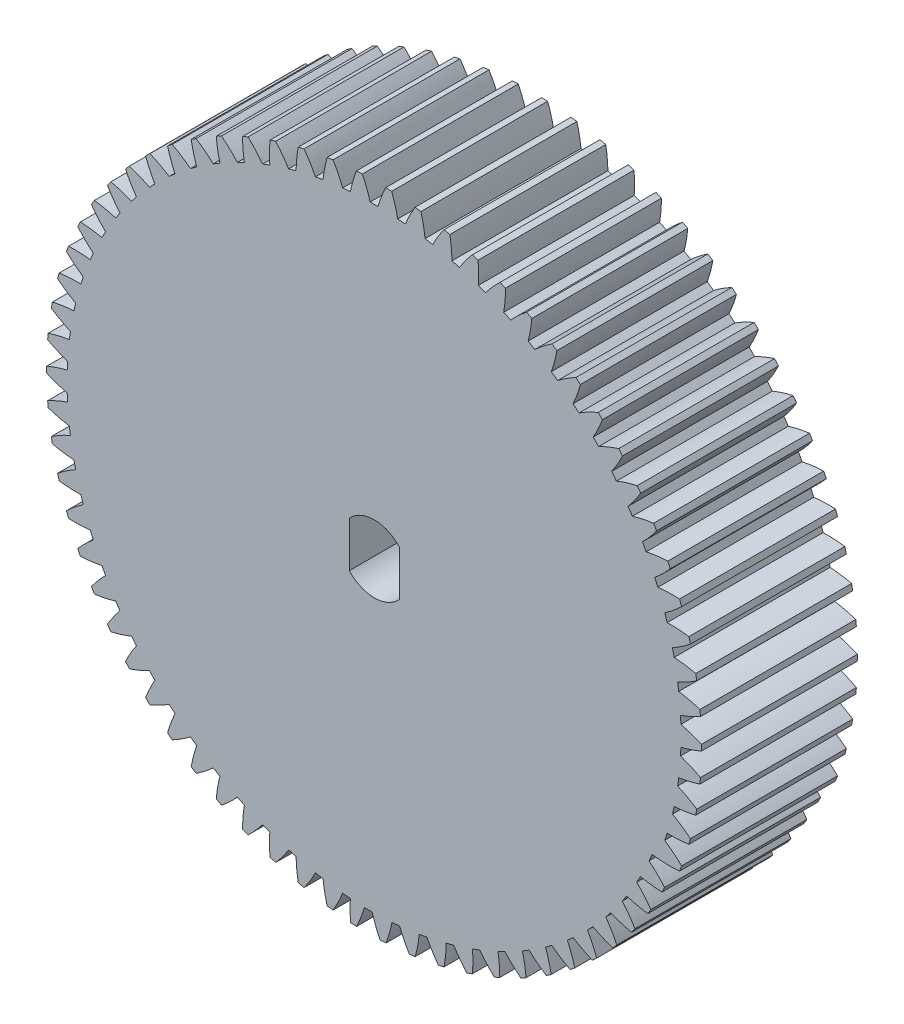
SolidWorks part; units mm, degrees
material "ABS"
ref_plane "Alzado" through (0, 0, 0) normal (0, 0, 1) x (1, 0, 0)
ref_plane "Planta" through (0, 0, 0) normal (0, 1, 0) x (1, 0, 0)
ref_plane "Vista lateral" through (0, 0, 0) normal (1, 0, 0) x (0, 0, -1)
sketch "Croquis1" plane through (0, 0, 0) normal (0, 0, 1) x (1, 0, 0)
  line L0 (-0.0534, 0.0662) -> (-0.0534, 2.6662) construction
  line L1 (-0.0534, 0.0662) -> (-0.0534, 2.6662) construction
  line L4 (-1.9784, 1.8138) -> (-1.9784, -1.6815)
  line L5 (1.8716, 1.8138) -> (1.8716, -1.6815)
  arc A0 (-25.274, -0.1619) -> (-23.6867, -0.6961) centre (-21.3661, 8.8252) ccw
  arc A1 (-23.6867, -0.6961) -> (-23.66, -1.2912) centre (-0.0534, 0.0662) ccw
  arc A2 (-23.66, -1.2912) -> (-25.193, -1.9655) centre (-20.4953, -10.5662) ccw
  arc A3 (-25.193, -1.9655) -> (-25.1521, -2.4198) centre (-0.075, 0.0662) ccw
  arc A4 (-25.1521, -2.4198) -> (-23.5233, -2.8095) centre (-22.0656, 6.8814) ccw
  arc A5 (-23.5233, -2.8095) -> (-23.4434, -3.3999) centre (-0.075, 0.0662) ccw
  arc A6 (-23.4434, -3.3999) -> (-24.9097, -4.2089) centre (-19.46, -12.3538) ccw
  arc A7 (-24.9097, -4.2089) -> (-24.8283, -4.6577) centre (-0.075, 0.0662) ccw
  arc A8 (-24.8283, -4.6577) -> (-23.1711, -4.8999) centre (-22.588, 4.8828) ccw
  arc A9 (-23.1711, -4.8999) -> (-23.0386, -5.4807) centre (-0.075, 0.0662) ccw
  arc A10 (-23.0386, -5.4807) -> (-24.4265, -6.4178) centre (-18.2686, -14.0415) ccw
  arc A11 (-24.4265, -6.4178) -> (-24.3052, -6.8576) centre (-0.075, 0.0662) ccw
  arc A12 (-24.3052, -6.8576) -> (-22.633, -6.9502) centre (-22.9291, 2.8453) ccw
  arc A13 (-22.633, -6.9502) -> (-22.4489, -7.5168) centre (-0.075, 0.0662) ccw
  arc A14 (-22.4489, -7.5168) -> (-23.7473, -8.5746) centre (-16.9308, -15.6156) ccw
  arc A15 (-23.7473, -8.5746) -> (-23.587, -9.0017) centre (-0.075, 0.0662) ccw
  arc A16 (-23.587, -9.0017) -> (-21.9133, -8.944) centre (-23.0862, 0.7855) ccw
  arc A17 (-21.9133, -8.944) -> (-21.6791, -9.4918) centre (-0.075, 0.0662) ccw
  arc A18 (-21.6791, -9.4918) -> (-22.8774, -10.6618) centre (-15.4572, -17.0634) ccw
  arc A19 (-22.8774, -10.6618) -> (-22.6795, -11.0728) centre (-0.075, 0.0662) ccw
  arc A20 (-22.6795, -11.0728) -> (-21.0177, -10.8653) centre (-23.0581, -1.2801) ccw
  arc A21 (-21.0177, -10.8653) -> (-20.7354, -11.3899) centre (-0.075, 0.0662) ccw
  arc A22 (-20.7354, -11.3899) -> (-21.824, -12.6626) centre (-13.8598, -18.3733) ccw
  arc A23 (-21.824, -12.6626) -> (-21.59, -13.0542) centre (-0.075, 0.0662) ccw
  arc A24 (-21.59, -13.0542) -> (-19.9535, -12.6986) centre (-22.8449, -3.3348) ccw
  arc A25 (-19.9535, -12.6986) -> (-19.6253, -13.1958) centre (-0.075, 0.0662) ccw
  arc A26 (-19.6253, -13.1958) -> (-20.5955, -14.5609) centre (-12.1514, -19.5347) ccw
  arc A27 (-20.5955, -14.5609) -> (-20.3273, -14.9299) centre (-0.075, 0.0662) ccw
  arc A28 (-20.3273, -14.9299) -> (-18.7292, -14.4291) centre (-22.4483, -5.3622) ccw
  arc A29 (-18.7292, -14.4291) -> (-18.3578, -14.8949) centre (-0.075, 0.0662) ccw
  arc A30 (-18.3578, -14.8949) -> (-19.2017, -16.3415) centre (-10.3458, -20.5383) ccw
  arc A31 (-19.2017, -16.3415) -> (-18.9016, -16.685) centre (-0.075, 0.0662) ccw
  arc A32 (-18.9016, -16.685) -> (-17.3548, -16.0429) centre (-21.8717, -7.3459) ccw
  arc A33 (-17.3548, -16.0429) -> (-16.9431, -16.4735) centre (-0.075, 0.0662) ccw
  arc A34 (-16.9431, -16.4735) -> (-17.6539, -17.9899) centre (-8.4575, -21.376) ccw
  arc A35 (-17.6539, -17.9899) -> (-17.3242, -18.3051) centre (-0.075, 0.0662) ccw
  arc A36 (-17.3242, -18.3051) -> (-15.8412, -17.527) centre (-21.1195, -9.2699) ccw
  arc A37 (-15.8412, -17.527) -> (-15.3926, -17.919) centre (-0.075, 0.0662) ccw
  arc A38 (-15.3926, -17.919) -> (-15.9646, -19.493) centre (-6.5017, -22.0411) ccw
  arc A39 (-15.9646, -19.493) -> (-15.608, -19.7774) centre (-0.075, 0.0662) ccw
  arc A40 (-15.608, -19.7774) -> (-14.2007, -18.8695) centre (-20.1979, -11.1187) ccw
  arc A41 (-14.2007, -18.8695) -> (-13.7187, -19.2196) centre (-0.075, 0.0662) ccw
  arc A42 (-13.7187, -19.2196) -> (-14.1474, -20.8386) centre (-4.4941, -22.5282) ccw
  arc A43 (-14.1474, -20.8386) -> (-13.7667, -21.0899) centre (-0.075, 0.0662) ccw
  arc A44 (-13.7667, -21.0899) -> (-12.4465, -20.0594) centre (-19.1143, -12.8775) ccw
  arc A45 (-12.4465, -20.0594) -> (-11.9351, -20.365) centre (-0.075, 0.0662) ccw
  arc A46 (-11.9351, -20.365) -> (-12.2169, -22.0159) centre (-2.451, -22.8334) ccw
  arc A47 (-12.2169, -22.0159) -> (-11.8151, -22.232) centre (-0.075, 0.0662) ccw
  arc A48 (-11.8151, -22.232) -> (-10.5926, -21.0874) centre (-17.8774, -14.5321) ccw
  arc A49 (-10.5926, -21.0874) -> (-10.0559, -21.3459) centre (-0.075, 0.0662) ccw
  arc A50 (-10.0559, -21.3459) -> (-10.1886, -23.0153) centre (-0.3887, -22.9542) ccw
  arc A51 (-10.1886, -23.0153) -> (-9.7691, -23.1946) centre (-0.075, 0.0662) ccw
  arc A52 (-9.7691, -23.1946) -> (-8.6541, -21.945) centre (-16.4972, -16.0691) ccw
  arc A53 (-8.6541, -21.945) -> (-8.0963, -22.1544) centre (-0.075, 0.0662) ccw
  arc A54 (-8.0963, -22.1544) -> (-8.0788, -23.829) centre (1.676, -22.8896) ccw
  arc A55 (-8.0788, -23.829) -> (-7.645, -23.97) centre (-0.075, 0.0662) ccw
  arc A56 (-7.645, -23.97) -> (-6.6465, -22.6254) centre (-14.9847, -17.4762) ccw
  arc A57 (-6.6465, -22.6254) -> (-6.0722, -22.7839) centre (-0.075, 0.0662) ccw
  arc A58 (-6.0722, -22.7839) -> (-5.9047, -24.4503) centre (3.7267, -22.6402) ccw
  arc A59 (-5.9047, -24.4503) -> (-5.4599, -24.5518) centre (-0.075, 0.0662) ccw
  arc A60 (-5.4599, -24.5518) -> (-4.586, -23.1232) centre (-13.3522, -18.7421) ccw
  arc A61 (-4.586, -23.1232) -> (-3.9998, -23.2295) centre (-0.075, 0.0662) ccw
  arc A62 (-3.9998, -23.2295) -> (-3.6836, -24.8741) centre (5.7468, -22.2081) ccw
  arc A63 (-3.6836, -24.8741) -> (-3.2315, -24.9354) centre (-0.075, 0.0662) ccw
  arc A64 (-3.2315, -24.9354) -> (-2.4891, -23.4342) centre (-11.6128, -19.8565) ccw
  arc A65 (-2.4891, -23.4342) -> (-1.8958, -23.4876) centre (-0.075, 0.0662) ccw
  arc A66 (-1.8958, -23.4876) -> (-1.875, -25.0972) centre (7.8807, -24.1662) ccw
  arc A67 (-1.875, -25.0972) -> (-1.4193, -25.1177) centre (-0.5166, 0.0662) ccw
  arc A68 (-1.4193, -25.1177) -> (-0.8145, -23.556) centre (-10.2221, -20.8106) ccw
  arc A69 (-0.8145, -23.556) -> (-0.2187, -23.556) centre (-0.5166, 0.0662) ccw
  arc A70 (-0.2187, -23.556) -> (0.3861, -25.1177) centre (9.1889, -20.8106) ccw
  arc A71 (0.3861, -25.1177) -> (0.8418, -25.0972) centre (-0.5166, 0.0662) ccw
  arc A72 (0.8418, -25.0972) -> (1.3042, -23.4876) centre (-8.3116, -21.5965) ccw
  arc A73 (1.3042, -23.4876) -> (1.8976, -23.4342) centre (-0.5166, 0.0662) ccw
  arc A74 (1.8976, -23.4342) -> (2.6399, -24.9354) centre (11.0212, -19.8565) ccw
  arc A75 (2.6399, -24.9354) -> (3.092, -24.8741) centre (-0.5166, 0.0662) ccw
  arc A76 (3.092, -24.8741) -> (3.4082, -23.2295) centre (-6.3384, -22.2081) ccw
  arc A77 (3.4082, -23.2295) -> (3.9944, -23.1232) centre (-0.5166, 0.0662) ccw
  arc A78 (3.9944, -23.1232) -> (4.8683, -24.5518) centre (12.7606, -18.7421) ccw
  arc A79 (4.8683, -24.5518) -> (5.3131, -24.4503) centre (-0.5166, 0.0662) ccw
  arc A80 (5.3131, -24.4503) -> (5.4806, -22.7839) centre (-4.3183, -22.6402) ccw
  arc A81 (5.4806, -22.7839) -> (6.0549, -22.6254) centre (-0.5166, 0.0662) ccw
  arc A82 (6.0549, -22.6254) -> (7.0534, -23.97) centre (14.3931, -17.4762) ccw
  arc A83 (7.0534, -23.97) -> (7.4872, -23.829) centre (-0.5166, 0.0662) ccw
  arc A84 (7.4872, -23.829) -> (7.5047, -22.1544) centre (-2.2676, -22.8896) ccw
  arc A85 (7.5047, -22.1544) -> (8.0625, -21.945) centre (-0.5166, 0.0662) ccw
  arc A86 (8.0625, -21.945) -> (9.1775, -23.1946) centre (15.9056, -16.0691) ccw
  arc A87 (9.1775, -23.1946) -> (9.597, -23.0153) centre (-0.5166, 0.0662) ccw
  arc A88 (9.597, -23.0153) -> (9.4643, -21.3459) centre (-0.2028, -22.9542) ccw
  arc A89 (9.4643, -21.3459) -> (10.001, -21.0874) centre (-0.5166, 0.0662) ccw
  arc A90 (10.001, -21.0874) -> (11.2236, -22.232) centre (17.2858, -14.5321) ccw
  arc A91 (11.2236, -22.232) -> (11.6253, -22.0159) centre (-0.5166, 0.0662) ccw
  arc A92 (11.6253, -22.0159) -> (11.3435, -20.365) centre (1.8594, -22.8334) ccw
  arc A93 (11.3435, -20.365) -> (11.8549, -20.0594) centre (-0.5166, 0.0662) ccw
  arc A94 (11.8549, -20.0594) -> (13.1751, -21.0899) centre (18.5227, -12.8775) ccw
  arc A95 (13.1751, -21.0899) -> (13.5558, -20.8386) centre (-0.5166, 0.0662) ccw
  arc A96 (13.5558, -20.8386) -> (13.1272, -19.2196) centre (3.9025, -22.5282) ccw
  arc A97 (13.1272, -19.2196) -> (13.6091, -18.8695) centre (-0.5166, 0.0662) ccw
  arc A98 (13.6091, -18.8695) -> (15.0164, -19.7774) centre (19.6063, -11.1187) ccw
  arc A99 (15.0164, -19.7774) -> (15.373, -19.493) centre (-0.5166, 0.0662) ccw
  arc A100 (15.373, -19.493) -> (14.801, -17.919) centre (5.9101, -22.0411) ccw
  arc A101 (14.801, -17.919) -> (15.2496, -17.527) centre (-0.5166, 0.0662) ccw
  arc A102 (15.2496, -17.527) -> (16.7326, -18.3051) centre (20.5279, -9.2699) ccw
  arc A103 (16.7326, -18.3051) -> (17.0623, -17.9899) centre (-0.5166, 0.0662) ccw
  arc A104 (17.0623, -17.9899) -> (16.3515, -16.4735) centre (7.8659, -21.376) ccw
  arc A105 (16.3515, -16.4735) -> (16.7632, -16.0429) centre (-0.5166, 0.0662) ccw
  arc A106 (16.7632, -16.0429) -> (18.31, -16.685) centre (21.2801, -7.3459) ccw
  arc A107 (18.31, -16.685) -> (18.6101, -16.3415) centre (-0.5166, 0.0662) ccw
  arc A108 (18.6101, -16.3415) -> (17.7662, -14.8949) centre (9.7542, -20.5383) ccw
  arc A109 (17.7662, -14.8949) -> (18.1376, -14.4291) centre (-0.5166, 0.0662) ccw
  arc A110 (18.1376, -14.4291) -> (19.7357, -14.9299) centre (21.8568, -5.3622) ccw
  arc A111 (19.7357, -14.9299) -> (20.0039, -14.5609) centre (-0.5166, 0.0662) ccw
  arc A112 (20.0039, -14.5609) -> (19.0337, -13.1958) centre (11.5599, -19.5347) ccw
  arc A113 (19.0337, -13.1958) -> (19.3619, -12.6986) centre (-0.5166, 0.0662) ccw
  arc A114 (19.3619, -12.6986) -> (20.9984, -13.0542) centre (22.2533, -3.3348) ccw
  arc A115 (20.9984, -13.0542) -> (21.2324, -12.6626) centre (-0.5166, 0.0662) ccw
  arc A116 (21.2324, -12.6626) -> (20.1438, -11.3899) centre (13.2682, -18.3733) ccw
  arc A117 (20.1438, -11.3899) -> (20.4261, -10.8653) centre (-0.5166, 0.0662) ccw
  arc A118 (20.4261, -10.8653) -> (22.0879, -11.0728) centre (22.4665, -1.2801) ccw
  arc A119 (22.0879, -11.0728) -> (22.2859, -10.6618) centre (-0.5166, 0.0662) ccw
  arc A120 (22.2859, -10.6618) -> (21.0875, -9.4918) centre (14.8656, -17.0634) ccw
  arc A121 (21.0875, -9.4918) -> (21.3217, -8.944) centre (-0.5166, 0.0662) ccw
  arc A122 (21.3217, -8.944) -> (23.437, -9.0017) centre (22.6447, 0.7663) ccw
  arc A123 (23.437, -9.0017) -> (23.5973, -8.5746) centre (-0.075, 0.0662) ccw
  arc A124 (23.5973, -8.5746) -> (22.2989, -7.5168) centre (16.7808, -15.6156) ccw
  arc A125 (22.2989, -7.5168) -> (22.483, -6.9502) centre (-0.075, 0.0662) ccw
  arc A126 (22.483, -6.9502) -> (24.1552, -6.8576) centre (22.7791, 2.8453) ccw
  arc A127 (24.1552, -6.8576) -> (24.2765, -6.4178) centre (-0.075, 0.0662) ccw
  arc A128 (24.2765, -6.4178) -> (22.8886, -5.4807) centre (18.1186, -14.0415) ccw
  arc A129 (22.8886, -5.4807) -> (23.0211, -4.8999) centre (-0.075, 0.0662) ccw
  arc A130 (23.0211, -4.8999) -> (24.6783, -4.6577) centre (22.438, 4.8828) ccw
  arc A131 (24.6783, -4.6577) -> (24.7597, -4.2089) centre (-0.075, 0.0662) ccw
  arc A132 (24.7597, -4.2089) -> (23.2934, -3.3999) centre (19.31, -12.3538) ccw
  arc A133 (23.2934, -3.3999) -> (23.3733, -2.8095) centre (-0.075, 0.0662) ccw
  arc A134 (23.3733, -2.8095) -> (25.0021, -2.4198) centre (21.9156, 6.8814) ccw
  arc A135 (25.0021, -2.4198) -> (25.043, -1.9655) centre (-0.075, 0.0662) ccw
  arc A136 (25.043, -1.9655) -> (23.51, -1.2912) centre (20.3453, -10.5662) ccw
  arc A137 (23.51, -1.2912) -> (23.5367, -0.6961) centre (-0.075, 0.0662) ccw
  arc A138 (23.5367, -0.6961) -> (25.124, -0.1619) centre (21.2161, 8.8252) ccw
  arc A139 (25.124, -0.1619) -> (25.124, 0.2942) centre (-0.075, 0.0662) ccw
  arc A140 (25.124, 0.2942) -> (23.5367, 0.8284) centre (21.2161, -8.6929) ccw
  arc A141 (23.5367, 0.8284) -> (23.51, 1.4235) centre (-0.075, 0.0662) ccw
  arc A142 (23.51, 1.4235) -> (25.043, 2.0978) centre (20.3453, 10.6985) ccw
  arc A143 (25.043, 2.0978) -> (25.0021, 2.5521) centre (-0.075, 0.0662) ccw
  arc A144 (25.0021, 2.5521) -> (23.3733, 2.9419) centre (21.9156, -6.7491) ccw
  arc A145 (23.3733, 2.9419) -> (23.2934, 3.5322) centre (-0.075, 0.0662) ccw
  arc A146 (23.2934, 3.5322) -> (24.7597, 4.3412) centre (19.31, 12.4861) ccw
  arc A147 (24.7597, 4.3412) -> (24.6783, 4.79) centre (-0.075, 0.0662) ccw
  arc A148 (24.6783, 4.79) -> (23.0211, 5.0322) centre (22.438, -4.7505) ccw
  arc A149 (23.0211, 5.0322) -> (22.8886, 5.613) centre (-0.075, 0.0662) ccw
  arc A150 (22.8886, 5.613) -> (24.2765, 6.5501) centre (18.1186, 14.1738) ccw
  arc A151 (24.2765, 6.5501) -> (24.1552, 6.9899) centre (-0.075, 0.0662) ccw
  arc A152 (24.1552, 6.9899) -> (22.483, 7.0825) centre (22.7791, -2.713) ccw
  arc A153 (22.483, 7.0825) -> (22.2989, 7.6491) centre (-0.075, 0.0662) ccw
  arc A154 (22.2989, 7.6491) -> (23.5973, 8.7069) centre (16.7808, 15.7479) ccw
  arc A155 (23.5973, 8.7069) -> (23.437, 9.134) centre (-0.075, 0.0662) ccw
  arc A156 (23.437, 9.134) -> (21.7633, 9.0763) centre (22.9362, -0.6532) ccw
  arc A157 (21.7633, 9.0763) -> (21.5291, 9.6241) centre (-0.075, 0.0662) ccw
  arc A158 (21.5291, 9.6241) -> (22.7274, 10.7941) centre (15.3072, 17.1957) ccw
  arc A159 (22.7274, 10.7941) -> (22.5295, 11.2051) centre (-0.075, 0.0662) ccw
  arc A160 (22.5295, 11.2051) -> (20.8677, 10.9976) centre (22.9081, 1.4124) ccw
  arc A161 (20.8677, 10.9976) -> (20.5854, 11.5223) centre (-0.075, 0.0662) ccw
  arc A162 (20.5854, 11.5223) -> (21.674, 12.7949) centre (13.7098, 18.5056) ccw
  arc A163 (21.674, 12.7949) -> (21.44, 13.1865) centre (-0.075, 0.0662) ccw
  arc A164 (21.44, 13.1865) -> (19.8035, 12.8309) centre (22.6949, 3.4672) ccw
  arc A165 (19.8035, 12.8309) -> (19.4753, 13.3281) centre (-0.075, 0.0662) ccw
  arc A166 (19.4753, 13.3281) -> (20.4455, 14.6932) centre (12.0014, 19.667) ccw
  arc A167 (20.4455, 14.6932) -> (20.1773, 15.0623) centre (-0.075, 0.0662) ccw
  arc A168 (20.1773, 15.0623) -> (18.5792, 14.5614) centre (22.2983, 5.4945) ccw
  arc A169 (18.5792, 14.5614) -> (18.2078, 15.0272) centre (-0.075, 0.0662) ccw
  arc A170 (18.2078, 15.0272) -> (19.0517, 16.4738) centre (10.1958, 20.6706) ccw
  arc A171 (19.0517, 16.4738) -> (18.7516, 16.8173) centre (-0.075, 0.0662) ccw
  arc A172 (18.7516, 16.8173) -> (17.2048, 16.1752) centre (21.7217, 7.4782) ccw
  arc A173 (17.2048, 16.1752) -> (16.7931, 16.6058) centre (-0.075, 0.0662) ccw
  arc A174 (16.7931, 16.6058) -> (17.5039, 18.1222) centre (8.3075, 21.5084) ccw
  arc A175 (17.5039, 18.1222) -> (17.1742, 18.4375) centre (-0.075, 0.0662) ccw
  arc A176 (17.1742, 18.4375) -> (15.6912, 17.6593) centre (20.9695, 9.4022) ccw
  arc A177 (15.6912, 17.6593) -> (15.2426, 18.0513) centre (-0.075, 0.0662) ccw
  arc A178 (15.2426, 18.0513) -> (15.8146, 19.6253) centre (6.3517, 22.1734) ccw
  arc A179 (15.8146, 19.6253) -> (15.458, 19.9097) centre (-0.075, 0.0662) ccw
  arc A180 (15.458, 19.9097) -> (14.0507, 19.0018) centre (20.0479, 11.2511) ccw
  arc A181 (14.0507, 19.0018) -> (13.5687, 19.3519) centre (-0.075, 0.0662) ccw
  arc A182 (13.5687, 19.3519) -> (13.9974, 20.9709) centre (4.3441, 22.6605) ccw
  arc A183 (13.9974, 20.9709) -> (13.6167, 21.2222) centre (-0.075, 0.0662) ccw
  arc A184 (13.6167, 21.2222) -> (12.2965, 20.1918) centre (18.9643, 13.0098) ccw
  arc A185 (12.2965, 20.1918) -> (11.7851, 20.4973) centre (-0.075, 0.0662) ccw
  arc A186 (11.7851, 20.4973) -> (12.0669, 22.1482) centre (2.301, 22.9657) ccw
  arc A187 (12.0669, 22.1482) -> (11.6651, 22.3643) centre (-0.075, 0.0662) ccw
  arc A188 (11.6651, 22.3643) -> (10.4426, 21.2197) centre (17.7274, 14.6644) ccw
  arc A189 (10.4426, 21.2197) -> (9.9059, 21.4782) centre (-0.075, 0.0662) ccw
  arc A190 (9.9059, 21.4782) -> (10.0386, 23.1477) centre (0.2387, 23.0865) ccw
  arc A191 (10.0386, 23.1477) -> (9.6191, 23.327) centre (-0.075, 0.0662) ccw
  arc A192 (9.6191, 23.327) -> (8.5041, 22.0773) centre (16.3472, 16.2014) ccw
  arc A193 (8.5041, 22.0773) -> (7.9463, 22.2867) centre (-0.075, 0.0662) ccw
  arc A194 (7.9463, 22.2867) -> (7.9288, 23.9613) centre (-1.826, 23.0219) ccw
  arc A195 (7.9288, 23.9613) -> (7.495, 24.1023) centre (-0.075, 0.0662) ccw
  arc A196 (7.495, 24.1023) -> (6.4965, 22.7578) centre (14.8347, 17.6085) ccw
  arc A197 (6.4965, 22.7578) -> (5.9222, 22.9163) centre (-0.075, 0.0662) ccw
  arc A198 (5.9222, 22.9163) -> (5.7547, 24.5826) centre (-3.8767, 22.7726) ccw
  arc A199 (5.7547, 24.5826) -> (5.3099, 24.6841) centre (-0.075, 0.0662) ccw
  arc A200 (5.3099, 24.6841) -> (4.436, 23.2555) centre (13.2022, 18.8744) ccw
  arc A201 (4.436, 23.2555) -> (3.8498, 23.3619) centre (-0.075, 0.0662) ccw
  arc A202 (3.8498, 23.3619) -> (3.5336, 25.0065) centre (-5.8968, 22.3404) ccw
  arc A203 (3.5336, 25.0065) -> (3.0815, 25.0677) centre (-0.075, 0.0662) ccw
  arc A204 (3.0815, 25.0677) -> (2.3391, 23.5665) centre (11.4628, 19.9889) ccw
  arc A205 (2.3391, 23.5665) -> (1.7458, 23.6199) centre (-0.075, 0.0662) ccw
  arc A206 (1.7458, 23.6199) -> (1.2834, 25.2295) centre (-7.87, 21.7288) ccw
  arc A207 (1.2834, 25.2295) -> (0.8277, 25.25) centre (-0.075, 0.0662) ccw
  arc A208 (0.8277, 25.25) -> (0.2229, 23.6883) centre (9.6305, 20.9429) ccw
  arc A209 (0.2229, 23.6883) -> (-0.3729, 23.6883) centre (-0.075, 0.0662) ccw
  arc A210 (-0.3729, 23.6883) -> (-0.9777, 25.25) centre (-9.7805, 20.9429) ccw
  arc A211 (-0.9777, 25.25) -> (-1.4334, 25.2295) centre (-0.075, 0.0662) ccw
  arc A212 (-1.4334, 25.2295) -> (-1.8958, 23.6199) centre (7.72, 21.7288) ccw
  arc A213 (-1.8958, 23.6199) -> (-2.4891, 23.5665) centre (-0.075, 0.0662) ccw
  arc A214 (-2.4891, 23.5665) -> (-3.2315, 25.0677) centre (-11.6128, 19.9889) ccw
  arc A215 (-3.2315, 25.0677) -> (-3.6836, 25.0065) centre (-0.075, 0.0662) ccw
  arc A216 (-3.6836, 25.0065) -> (-3.9998, 23.3619) centre (5.7468, 22.3404) ccw
  arc A217 (-3.9998, 23.3619) -> (-4.586, 23.2555) centre (-0.075, 0.0662) ccw
  arc A218 (-4.586, 23.2555) -> (-5.4599, 24.6841) centre (-13.3522, 18.8744) ccw
  arc A219 (-5.4599, 24.6841) -> (-5.9047, 24.5826) centre (-0.075, 0.0662) ccw
  arc A220 (-5.9047, 24.5826) -> (-6.0722, 22.9163) centre (3.7267, 22.7726) ccw
  arc A221 (-6.0722, 22.9163) -> (-6.6465, 22.7578) centre (-0.075, 0.0662) ccw
  arc A222 (-6.6465, 22.7578) -> (-7.645, 24.1023) centre (-14.9847, 17.6085) ccw
  arc A223 (-7.645, 24.1023) -> (-8.0788, 23.9613) centre (-0.075, 0.0662) ccw
  arc A224 (-8.0788, 23.9613) -> (-8.0963, 22.2867) centre (1.676, 23.0219) ccw
  arc A225 (-8.0963, 22.2867) -> (-8.6541, 22.0773) centre (-0.075, 0.0662) ccw
  arc A226 (-8.6541, 22.0773) -> (-9.7691, 23.327) centre (-16.4972, 16.2014) ccw
  arc A227 (-9.7691, 23.327) -> (-10.1886, 23.1477) centre (-0.075, 0.0662) ccw
  arc A228 (-10.1886, 23.1477) -> (-10.0559, 21.4782) centre (-0.3887, 23.0865) ccw
  arc A229 (-10.0559, 21.4782) -> (-10.5926, 21.2197) centre (-0.075, 0.0662) ccw
  arc A230 (-10.5926, 21.2197) -> (-11.8151, 22.3643) centre (-17.8774, 14.6644) ccw
  arc A231 (-11.8151, 22.3643) -> (-12.2169, 22.1482) centre (-0.075, 0.0662) ccw
  arc A232 (-12.2169, 22.1482) -> (-11.9351, 20.4973) centre (-2.451, 22.9657) ccw
  arc A233 (-11.9351, 20.4973) -> (-12.4465, 20.1918) centre (-0.075, 0.0662) ccw
  arc A234 (-12.4465, 20.1918) -> (-13.7667, 21.2222) centre (-19.1143, 13.0098) ccw
  arc A235 (-13.7667, 21.2222) -> (-14.1474, 20.9709) centre (-0.075, 0.0662) ccw
  arc A236 (-14.1474, 20.9709) -> (-13.7187, 19.3519) centre (-4.4941, 22.6605) ccw
  arc A237 (-13.7187, 19.3519) -> (-14.2007, 19.0018) centre (-0.075, 0.0662) ccw
  arc A238 (-14.2007, 19.0018) -> (-15.608, 19.9097) centre (-20.1979, 11.2511) ccw
  arc A239 (-15.608, 19.9097) -> (-15.9646, 19.6253) centre (-0.075, 0.0662) ccw
  arc A240 (-15.9646, 19.6253) -> (-15.3926, 18.0513) centre (-6.5017, 22.1734) ccw
  arc A241 (-15.3926, 18.0513) -> (-15.8412, 17.6593) centre (-0.075, 0.0662) ccw
  arc A242 (-15.8412, 17.6593) -> (-17.3242, 18.4375) centre (-21.1195, 9.4022) ccw
  arc A243 (-17.3242, 18.4375) -> (-17.6539, 18.1222) centre (-0.075, 0.0662) ccw
  arc A244 (-17.6539, 18.1222) -> (-16.9431, 16.6058) centre (-8.4575, 21.5084) ccw
  arc A245 (-16.9431, 16.6058) -> (-17.3548, 16.1752) centre (-0.075, 0.0662) ccw
  arc A246 (-17.3548, 16.1752) -> (-18.9016, 16.8173) centre (-21.8717, 7.4782) ccw
  arc A247 (-18.9016, 16.8173) -> (-19.2017, 16.4738) centre (-0.075, 0.0662) ccw
  arc A248 (-19.2017, 16.4738) -> (-18.3578, 15.0272) centre (-10.3458, 20.6706) ccw
  arc A249 (-18.3578, 15.0272) -> (-18.7292, 14.5614) centre (-0.075, 0.0662) ccw
  arc A250 (-18.7292, 14.5614) -> (-20.3273, 15.0623) centre (-22.4483, 5.4945) ccw
  arc A251 (-20.3273, 15.0623) -> (-20.5955, 14.6932) centre (-0.075, 0.0662) ccw
  arc A252 (-20.5955, 14.6932) -> (-19.6253, 13.3281) centre (-12.1514, 19.667) ccw
  arc A253 (-19.6253, 13.3281) -> (-19.9535, 12.8309) centre (-0.075, 0.0662) ccw
  arc A254 (-19.9535, 12.8309) -> (-21.59, 13.1865) centre (-22.8449, 3.4672) ccw
  arc A255 (-21.59, 13.1865) -> (-21.824, 12.7949) centre (-0.075, 0.0662) ccw
  arc A256 (-21.824, 12.7949) -> (-20.7354, 11.5223) centre (-13.8598, 18.5056) ccw
  arc A257 (-20.7354, 11.5223) -> (-21.0177, 10.9976) centre (-0.075, 0.0662) ccw
  arc A258 (-21.0177, 10.9976) -> (-22.6795, 11.2051) centre (-23.0581, 1.4124) ccw
  arc A259 (-22.6795, 11.2051) -> (-22.8774, 10.7941) centre (-0.075, 0.0662) ccw
  arc A260 (-22.8774, 10.7941) -> (-21.6791, 9.6241) centre (-15.4572, 17.1957) ccw
  arc A261 (-21.6791, 9.6241) -> (-21.9133, 9.0763) centre (-0.075, 0.0662) ccw
  arc A262 (-21.9133, 9.0763) -> (-23.587, 9.134) centre (-23.0862, -0.6532) ccw
  arc A263 (-23.587, 9.134) -> (-23.7473, 8.7069) centre (-0.075, 0.0662) ccw
  arc A264 (-23.7473, 8.7069) -> (-22.4489, 7.6491) centre (-16.9308, 15.7479) ccw
  arc A265 (-22.4489, 7.6491) -> (-22.633, 7.0825) centre (-0.075, 0.0662) ccw
  arc A266 (-22.633, 7.0825) -> (-24.3052, 6.9899) centre (-22.9291, -2.713) ccw
  arc A267 (-24.3052, 6.9899) -> (-24.4265, 6.5501) centre (-0.075, 0.0662) ccw
  arc A268 (-24.4265, 6.5501) -> (-23.0386, 5.613) centre (-18.2686, 14.1738) ccw
  arc A269 (-23.0386, 5.613) -> (-23.1711, 5.0322) centre (-0.075, 0.0662) ccw
  arc A270 (-23.1711, 5.0322) -> (-24.8283, 4.79) centre (-22.588, -4.7505) ccw
  arc A271 (-24.8283, 4.79) -> (-24.9097, 4.3412) centre (-0.075, 0.0662) ccw
  arc A272 (-24.9097, 4.3412) -> (-23.4434, 3.5322) centre (-19.46, 12.4861) ccw
  arc A273 (-23.4434, 3.5322) -> (-23.5233, 2.9419) centre (-0.075, 0.0662) ccw
  arc A274 (-23.5233, 2.9419) -> (-25.1521, 2.5521) centre (-22.0656, -6.7491) ccw
  arc A275 (-25.1521, 2.5521) -> (-25.193, 2.0978) centre (-0.075, 0.0662) ccw
  arc A276 (-25.193, 2.0978) -> (-23.66, 1.4235) centre (-20.4953, 10.6985) ccw
  arc A277 (-23.66, 1.4235) -> (-23.6867, 0.8284) centre (-0.075, 0.0662) ccw
  arc A278 (-23.6867, 0.8284) -> (-25.274, 0.2942) centre (-21.3661, -8.6929) ccw
  arc A279 (-25.274, 0.2942) -> (-25.274, -0.1619) centre (-0.075, 0.0662) ccw
  arc A282 (-1.9784, -1.6815) -> (1.8716, -1.6815) centre (-0.0534, 0.0662) ccw
  arc A283 (1.8716, 1.8138) -> (-1.9784, 1.8138) centre (-0.0534, 0.0662) ccw
  point P564 (0.0216, 2.7)
  dimension "D1" = 23.624
  dimension "D2" = 25.2
  dimension "D3" = 5.2
  dimension "D4" = 3.85
extrude "Saliente-Extruir1" add sketch "Croquis1" along normal blind 12
sketch "Croquis2" plane through (0, 0, 12) normal (0, 0, 1) x (1, 0, 0)
  circle A0 centre (0, 0) radius 23.5416
